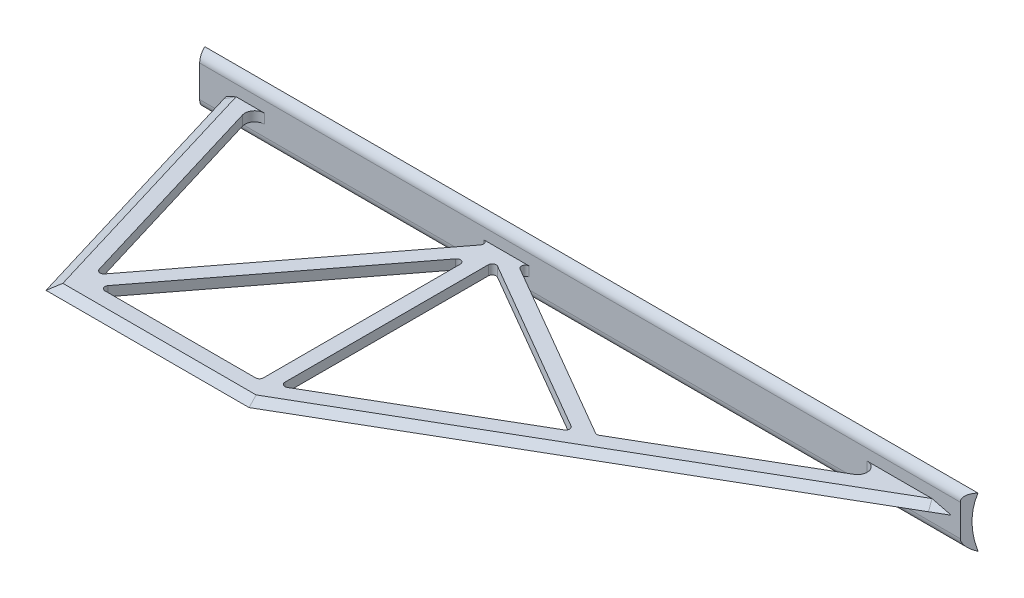
SolidWorks part; units mm, degrees
material "6061 Alloy"
ref_plane "Front Plane" through (0, 0, 0) normal (0, 0, 1) x (1, 0, 0)
ref_plane "Top Plane" through (0, 0, 0) normal (0, 1, 0) x (1, 0, 0)
ref_plane "Right Plane" through (0, 0, 0) normal (1, 0, 0) x (0, 0, -1)
sketch "CS path" plane through (0, 0, 0) normal (0, 1, 0) x (1, 0, 0)
  line L0 (-228.6, 0) -> (228.6, 0) construction
  line L1 (-115.8864, -163.068) -> (0, 0) construction
  line L2 (-52.3864, -163.068) -> (228.6, 0)
  line L3 (-228.6, 0) -> (-235.9387, 24.3167) construction
  line L4 (228.6, 0) -> (294.5056, 38.2477) construction
  line L5 (228.6, 0) -> (294.5056, 38.2477)
  line L6 (-179.3864, -163.068) -> (-52.3864, -163.068)
  line L8 (-228.6, 0) -> (-235.9387, 24.3167)
  line L9 (-179.3864, -163.068) -> (-228.6, 0) construction
  line L12 (-179.3864, -163.068) -> (-228.6, 0)
  dimension "D1" = 163.068
  dimension "D2" = 127
  dimension "D3" = 457.2
  dimension "D4" = 54.6
  dimension "D5" = 0
  dimension "D6" = 25.4
  dimension "D7" = 76.2
sketch "Sketch8" plane through (0, 0, 0) normal (1, 0, 0) x (0, 0, -1)
  line L0 (0, 0) -> (82.804, 0) construction
  line L1 (82.804, 0) -> (-43.02, 26.7447) construction
  line L2 (82.804, 0) -> (-44.9942, -27.1644) construction
  line L3 (4.8299, 16.5739) -> (0, 17.6005)
  line L4 (4.8299, -16.5739) -> (0, -17.6005)
  line L5 (0, 17.6005) -> (0, -17.6005)
  line L6 (3.175, 0) -> (86.995, 0) construction
  arc A0 (4.8299, 16.5739) -> (4.8299, -16.5739) centre (86.995, 0) ccw
  dimension "D1" = 12
  dimension "D2" = 12
extrude "Boss-Extrude3" add sketch "Sketch8" along normal blind 254 and the other way blind 254 separate body
ref_plane "Plane7" through (0, 17.6005, 0) normal (0, -1, 0) x (1, 0, 0)
ref_plane "Plane8" through (294.5056, 0, -38.2477) normal (0.8649, 0, -0.5019) x (-0.5019, 0, -0.8649)
sketch "Sketch9" plane through (294.5056, 0, -38.2477) normal (0.8649, 0, -0.5019) x (-0.5019, 0, -0.8649)
  line L1 (0, 3.175) -> (9.525, 3.175)
  line L3 (0, -3.175) -> (9.525, -3.175)
  line L4 (9.525, 3.175) -> (9.525, -3.175)
  line L6 (0, 3.175) -> (-6.35, 0)
  line L7 (-6.35, 0) -> (0, -3.175)
  dimension "D3" = 9.525
sweep "Sweep2" add profiles "Sketch9" path "CS path"
sketch "Sketch11" plane through (-254, 0, 0) normal (-1, 0, 0) x (0, 0, 1)
  line L0 (-55.6299, -16.5739) -> (-55.6299, 16.5739)
  line L1 (-4.8299, 16.5739) -> (-55.6299, 16.5739)
  line L2 (-4.8299, -16.5739) -> (-55.6299, -16.5739)
  arc A0 (-4.8299, 16.5739) -> (-4.8299, -16.5739) centre (-86.995, 0) cw
  dimension "D1" = 50.8
extrude "Cut-Extrude1" cut sketch "Sketch11" against normal blind 762
sketch "Sketch12" plane through (0, 3.175, 0) normal (0, 1, 0) x (1, 0, 0)
  line L0 (-54.9501, -153.543) -> (-54.9501, 0) construction
  line L1 (-254, 0) -> (254, 0) construction
  line L2 (-54.9501, 0) -> (-172.3117, -153.543) construction
  line L3 (77.3368, -76.7715) -> (-54.9501, 0) construction
  line L4 (-60.9445, 0) -> (-174.0085, -147.9206)
  line L5 (-50.1876, -150.7791) -> (-50.1876, -8.2703)
  line L6 (82.0809, -74.0183) -> (-45.4618, 0)
  line L7 (-218.6507, 0) -> (-172.3117, -153.543)
  line L8 (-172.3117, -153.543) -> (-54.9501, -153.543)
  line L9 (-54.9501, -153.543) -> (209.6236, 0)
  line L10 (209.6236, 0) -> (-218.6507, 0)
  line L12 (-59.7126, -153.543) -> (-59.7126, -14.0731)
  line L13 (72.5927, -79.5247) -> (-50.1876, -8.2703)
  line L15 (-58.7338, 2.8921) -> (-176.0955, -150.6509) construction
  line L16 (74.9463, -80.8906) -> (-57.3405, -4.1191) construction
  line L17 (79.7273, -72.6524) -> (-52.5596, 4.1191) construction
  line L18 (-50.1876, -153.543) -> (-50.1876, 0) construction
  line L19 (-59.7126, -14.0731) -> (-166.3173, -153.543)
  line L20 (-59.7126, -153.543) -> (-59.7126, 0) construction
  line M9 (-172.3117, -153.543) -> (-218.6507, 0)
  dimension "D1" = 4.7625
  dimension "D2" = 4.7625
extrude "Boss-Extrude4" add sketch "Sketch12" against normal blind 6.35 contours L19 L12 L8 L9 L5 L13 L6 L10 L4 M9 region at (-57.0565, 3.175, 66.3758)
fillet "Fillet1" radius 2.54 10 edges at (82.0809, 0, 74.0183) (-174.0085, 0, 147.9206) (-59.7126, 0, 153.543) (-166.3173, 0, 153.543) (-50.1876, 0, 150.7791) (72.5927, 0, 79.5247) (-59.7126, 0, 14.0731) (-50.1876, 0, 8.2703) (-60.9445, 0, 0) (-45.4618, 0, 0)
fillet "Fillet2" radius 6.35 2 edges at (209.6236, 0, 0) (-218.6507, 0, 0)
fillet "Fillet3" radius 6.35 2 edges at (0, -17.6005, 0) (0, 17.6005, 0)
ref_plane "Plane9" through (0, 16.5739, 0) normal (0, 1, 0) x (1, 0, 0)
sketch "Sketch13" plane through (0, 16.5739, 0) normal (0, 1, 0) x (1, 0, 0)
  line L0 (-254, 4.8299) -> (-254, 0)
  line L1 (254, 0) -> (-254, 0) construction
  line L2 (-254, 4.8299) -> (-254, 0) construction
  line L3 (-254, 0) -> (-252.5427, 0)
  line L4 (-252.5427, 0) -> (-254, 4.8299)
  line L5 (254, 4.8299) -> (254, 0)
  line L6 (254, 0) -> (247.2036, 0)
  line L7 (247.2036, 0) -> (254, 4.8299)
  line L9 (-184.1029, -169.418) -> (-234.6792, -1.8347) construction
  line L11 (-254, 4.8299) -> (254, 4.8299) construction
  dimension "D1" = 4.8299
  dimension "D2" = 73.21
  dimension "D3" = 54.6
  dimension "D4" = 73.206
extrude "Cut-Extrude2" cut sketch "Sketch13" against normal blind 50.8
